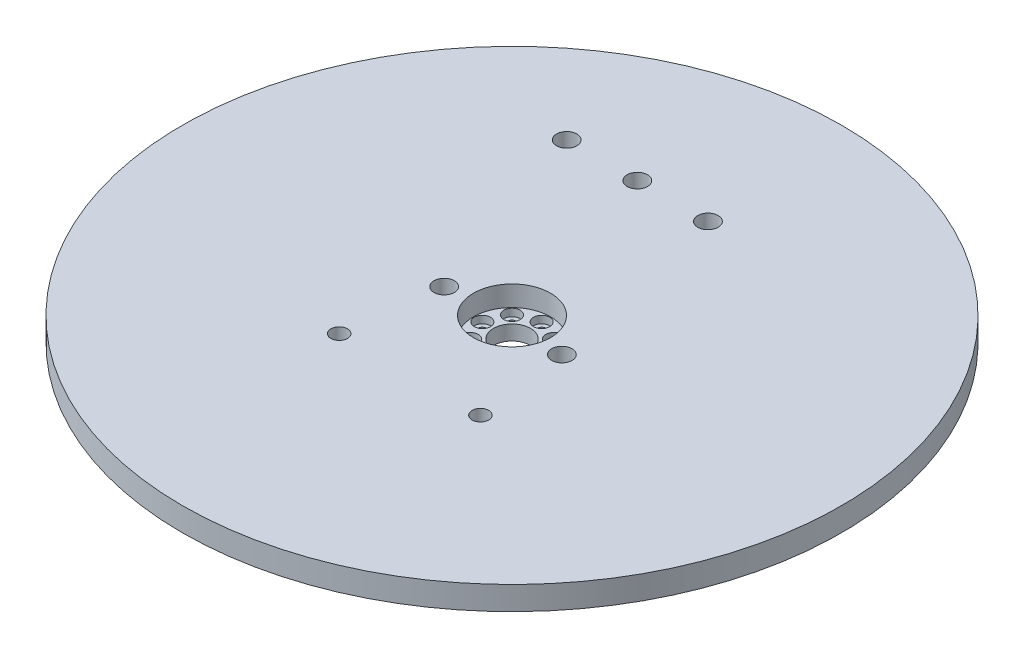
SolidWorks part; units mm, degrees
other "Markup1"
sketch "Sketch21" plane through (-65.5, -15.05, -60) normal (-0.0927, -0.2854, -0.9539) x (0.9951, -0.0609, -0.0785)
material "6061 Alloy"
ref_plane "Front Plane" through (0, 0, 0) normal (0, 0, 1) x (1, 0, 0)
ref_plane "Top Plane" through (0, 0, 0) normal (0, 1, 0) x (1, 0, 0)
ref_plane "Right Plane" through (0, 0, 0) normal (1, 0, 0) x (0, 0, -1)
sketch "Sketch1" plane through (0, 0, 0) normal (0, 1, 0) x (1, 0, 0)
  circle A0 centre (0, 0) radius 88.9
  dimension "D1" = 177.8
extrude "Boss-Extrude1" add sketch "Sketch1" along normal mid plane 6.35
sketch "Sketch2" plane through (0, -3.175, 0) normal (0, -1, 0) x (1, 0, 0)
  circle A0 centre (0, 0) radius 12.065
  circle A1 centre (0, 0) radius 88.9 construction
  dimension "D1" = 24.13
extrude "Boss-Extrude2" add sketch "Sketch2" along normal blind 3.175
sketch "Sketch5" plane through (0, 3.175, 0) normal (0, 1, 0) x (1, 0, 0)
  circle A0 centre (0, 0) radius 10.4
  circle A1 centre (0, 0) radius 88.9 construction
  dimension "D1" = 20.8
extrude "Cut-Extrude1" cut sketch "Sketch5" against normal offset from surface (5.525 mm away) 4 up to face at (0, -6.35, -12.065)
sketch "Sketch6" plane through (0, -2.35, 0) normal (0, 1, 0) x (1, 0, 0)
  circle A0 centre (0, 0) radius 5
  circle A1 centre (0, 0) radius 10.4 construction
  dimension "D1" = 10
extrude "Cut-Extrude2" cut sketch "Sketch6" along direction (0, -1, 0) on the side against the normal up to next (4 mm away)
sketch "Sketch15" plane through (0, -6.35, 0) normal (0, 1, 0) x (1, 0, 0)
  circle A0 centre (0, 8) radius 1
  circle A1 centre (-5.6569, 5.6569) radius 1
  circle A2 centre (5.6569, 5.6569) radius 1
  circle A3 centre (-5.6569, -5.6569) radius 1
  circle A4 centre (5.6569, -5.6569) radius 1
  circle A5 centre (-8, 0) radius 1
  circle A6 centre (0, -8) radius 1
  circle A7 centre (8, 0) radius 1
  circle A8 centre (0, 0) radius 4
  circle A9 centre (0, 0) radius 11
  circle A10 centre (0, 0) radius 2.25
  circle A11 centre (0, 0) radius 5
  circle A12 centre (0, 0) radius 5 construction
  dimension "D1" = 4.5
  dimension "D2" = 8
  dimension "D3" = 10
  dimension "D4" = 22
  dimension "D5" = 2
  dimension "D6" = 8
  dimension "D7" = 5.6569
  dimension "D8" = 8
  dimension "D9" = 5.6569
  dimension "D10" = 5.6569
  dimension "D11" = 8
  dimension "D12" = 5.6569
  dimension "D13" = 8
hole_wizard "CBORE for M2 SHCS1" positions "Sketch19" profile "Sketch20" counterbore size "M2" standard "ANSI Metric"
sketch "Sketch19" plane through (0, -2.35, 0) normal (0, 1, 0) x (1, 0, 0)
  point P0 (-5.6569, 5.6569)
  point P3 (0, 8)
  point P6 (5.6569, 5.6569)
  point P9 (8, 0)
  point P12 (5.6569, -5.6569)
  point P15 (0, -8)
  point P18 (-5.6569, -5.6569)
  point P21 (-8, 0)
sketch "Sketch20" plane through (-5.6569, -2.35, -5.6569) normal (1, 0, 0) x (0, 0, 1)
  line L0 (0, 0) -> (0, 6.6609)
  line L1 (0, 6.6609) -> (1.1, 6)
  line L2 (1.1, 6) -> (1.1, 2)
  line L3 (1.1, 2) -> (2.2, 2)
  line L4 (2.2, 2) -> (2.2, 0)
  line L5 (2.2, 0) -> (0, 0)
  line L10 (0, 6.6609) -> (-1.1, 6) construction
  line L11 (0, -6.35) -> (0, 107.95) construction
  dimension "Hole Dia." = 2.2
  dimension "Hole Depth" = 6
  dimension "C'Bore Dia." = 4.4
  dimension "C'Bore Depth" = 2
  dimension "Drill Angle" = 118
hole_wizard "M5 Clearance Hole1" positions "Sketch24" profile "Sketch25" hole size "M5" standard "ANSI Metric" end condition through all
sketch "Sketch24" plane through (0, 3.175, 0) normal (0, 1, 0) x (1, 0, 0)
  point P0 (-15.875, -2.4257)
  point P3 (15.875, -2.4257)
  point P6 (4.4672, 48.3914)
  point P9 (-14.5828, 48.3914)
  point P12 (-33.6328, 48.3914)
sketch "Sketch25" plane through (-15.875, 3.175, 2.4257) normal (1, 0, 0) x (0, 0, 1)
  line L0 (0, 0) -> (0, 9.525)
  line L1 (0, 9.525) -> (2.75, 9.525)
  line L2 (2.75, 9.525) -> (2.75, 0)
  line L5 (2.75, 0) -> (0, 0)
  line L11 (0, -6.35) -> (0, 107.95) construction
  dimension "Thru Hole Dia." = 5.5
  dimension "Thru Hole Depth" = 9.525
hole_wizard "M4 Clearance Hole1" positions "Sketch26" profile "Sketch27" hole size "M4" standard "ANSI Metric" end condition through all
sketch "Sketch26" plane through (0, 3.175, 0) normal (0, 1, 0) x (1, 0, 0)
  point P0 (19.05, -27.5642)
  point P3 (-19.05, -27.5642)
sketch "Sketch27" plane through (19.05, 3.175, 27.5642) normal (1, 0, 0) x (0, 0, 1)
  line L0 (0, 0) -> (0, 9.525)
  line L1 (0, 9.525) -> (2.25, 9.525)
  line L2 (2.25, 9.525) -> (2.25, 0)
  line L5 (2.25, 0) -> (0, 0)
  line L11 (0, -6.35) -> (0, 107.95) construction
  dimension "Thru Hole Dia." = 4.5
  dimension "Thru Hole Depth" = 9.525
